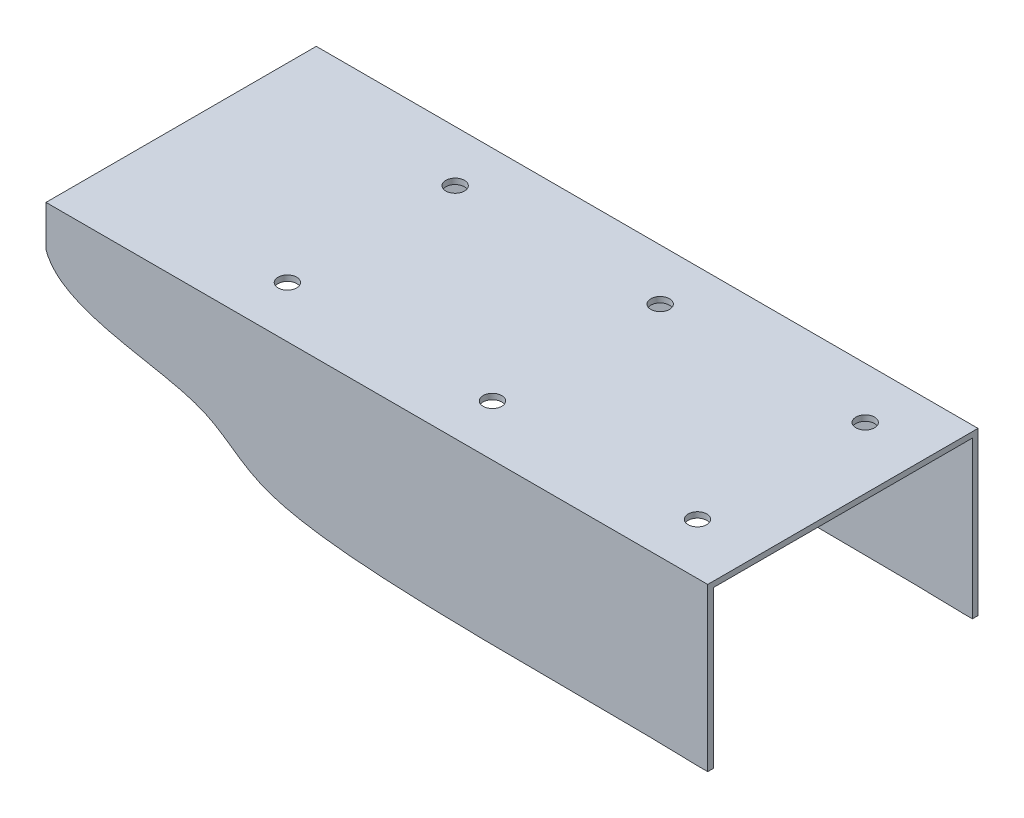
SolidWorks part; units mm, degrees
ref_plane "Спереди" through (0, 0, 0) normal (0, 0, 1) x (1, 0, 0)
ref_plane "Сверху" through (0, 0, 0) normal (0, 1, 0) x (1, 0, 0)
ref_plane "Справа" through (0, 0, 0) normal (1, 0, 0) x (0, 0, -1)
sketch "Эскиз1" plane through (0, 0, 0) normal (1, 0, 0) x (0, 0, -1)
  line L0 (0, 0) -> (0, 87)
  line L1 (0, 87) -> (145, 87)
  line L2 (145, 87) -> (145, 0)
extrude "Вытянуть-Тонкостенный1" add sketch "Эскиз1" along normal blind 355 thin thin type one direction wall 3
sketch "Эскиз2" plane through (0, 0, 0) normal (0, 0, 1) x (1, 0, 0)
  line L0 (0, 65.1241) -> (0, 0)
  line L1 (0, 0) -> (0, 87) construction
  line L2 (0, 0) -> (350.2785, 0)
  line L3 (355, 0) -> (0, 0) construction
  spline S0 degree 3 poles (0, 65.1241) (7.9338, 41.7869) (88.8356, 42.672) (115.5486, -4.5707) (275.8086, 2.4518) (350.2785, 0) knots 0 0 0 0 0.332901 0.537301 1 1 1 1
extrude "Вырез-Вытянуть1" cut sketch "Эскиз2" against normal through all
sketch "Эскиз3" plane through (0, 87, 0) normal (0, 1, 0) x (1, 0, 0)
  circle A0 centre (322, 117.5) radius 5
  circle A1 centre (212, 117.5) radius 5
  circle A2 centre (102, 117.5) radius 5
  circle A3 centre (212, 27.5) radius 5
  circle A4 centre (102, 27.5) radius 5
  circle A5 centre (322, 27.5) radius 5
  dimension "D1" = 3
  dimension "D2" = 2
extrude "Вырез-Вытянуть2" cut sketch "Эскиз3" against normal blind 10
